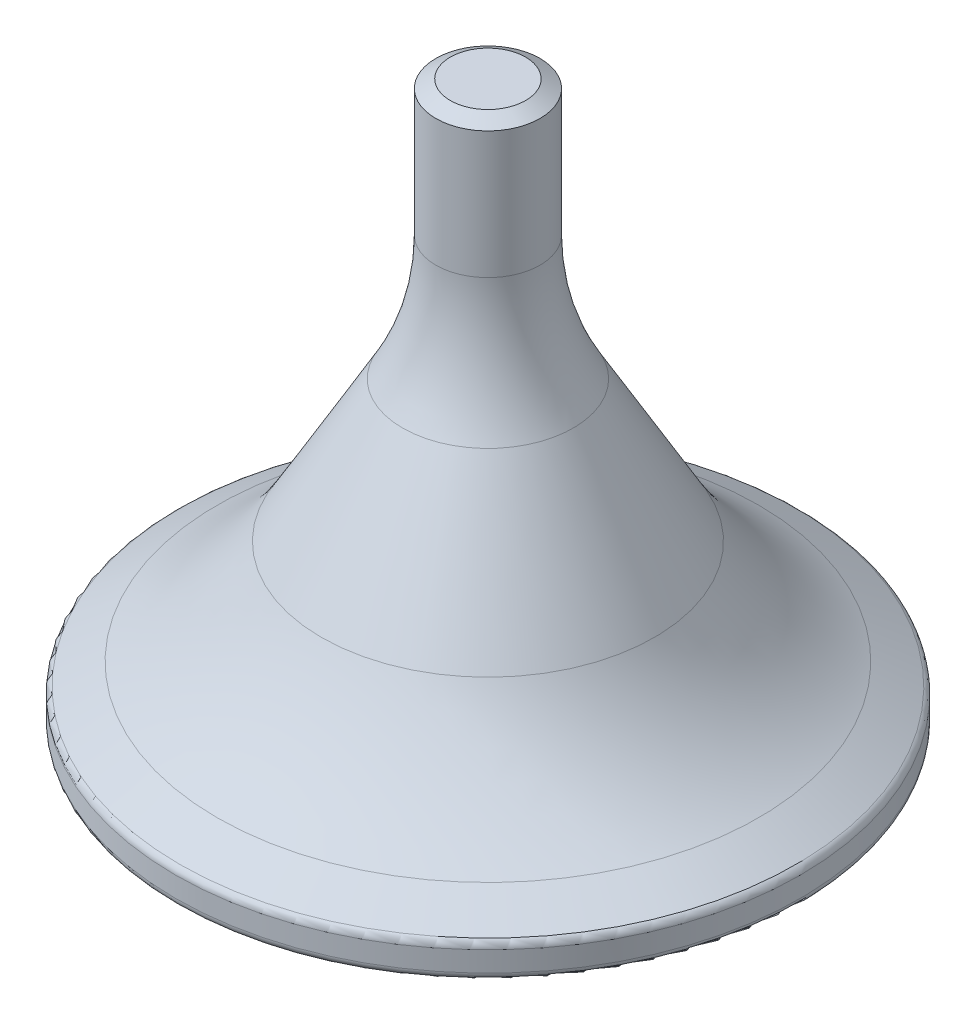
SolidWorks part; units mm, degrees
material "6061-T6 (SS)"
ref_plane "Front Plane" through (0, 0, 0) normal (0, 0, 1) x (1, 0, 0)
ref_plane "Top Plane" through (0, 0, 0) normal (0, 1, 0) x (1, 0, 0)
ref_plane "Right Plane" through (0, 0, 0) normal (1, 0, 0) x (0, 0, -1)
sketch "Sketch3" plane through (0, 0, 0) normal (1, 0, 0) x (0, 0, -1)
  line L0 (0, 0) -> (0, -43.2471) construction
  line L1 (0, 0) -> (3.175, 0)
  line L2 (3.175, 0) -> (3.175, -8.255)
  line L4 (19.05, -32.2338) -> (19.05, -34.2658)
  line L5 (19.05, -34.2658) -> (0, -34.2658)
  line L6 (0, -34.2658) -> (0, 0)
  line L7 (5.207, -15.8385) -> (10.16, -24.4174)
  line L8 (16.51, -30.7674) -> (19.05, -32.2338)
  arc A0 (3.175, -8.255) -> (5.207, -15.8385) centre (18.3421, -8.255) ccw
  arc A1 (10.16, -24.4174) -> (16.51, -30.7674) centre (25.1843, -15.7431) ccw
  dimension "D2" = 30
  dimension "D6" = 30
  dimension "D1" = 6.35
  dimension "D3" = 8.255
  dimension "D4" = 2.032
  dimension "D5" = 38.1
  dimension "D7" = 2.54
  dimension "D8" = 2.032
  dimension "D9" = 6.35
  dimension "D10" = 34.2658
revolve "Revolve1" add sketch "Sketch3" angle 360 about L0
fillet "Fillet1" radius 0.508 2 edges at (0, -32.2338, 19.05) (0, -34.2658, 19.05)
chamfer "Chamfer1" distance 0.508 angle 60 1 edges at (0, 0, 3.175) first distance on face at (0, 0, 3.175)
sketch "Sketch4" plane through (0, -34.2658, 0) normal (0, -1, 0) x (1, 0, 0)
  line L1 (-9.525, 1.5875) -> (9.525, 1.5875)
  line L2 (-9.525, 1.5875) -> (-9.525, -1.5875)
  line L3 (-9.525, -1.5875) -> (9.525, -1.5875)
  line L4 (9.525, 1.5875) -> (9.525, -1.5875)
  point P4 (-9.525, 0)
  point P5 (0, -1.5875)
  dimension "D1" = 3.175
  dimension "D2" = 19.05
extrude "Cut-Extrude1" cut sketch "Sketch4" against normal blind 4.7625
fillet "Fillet2" radius 1.5875 4 edges at (-9.525, -31.8846, -1.5875) (9.525, -31.8846, -1.5875) (9.525, -31.8846, 1.5875) (-9.525, -31.8846, 1.5875)
